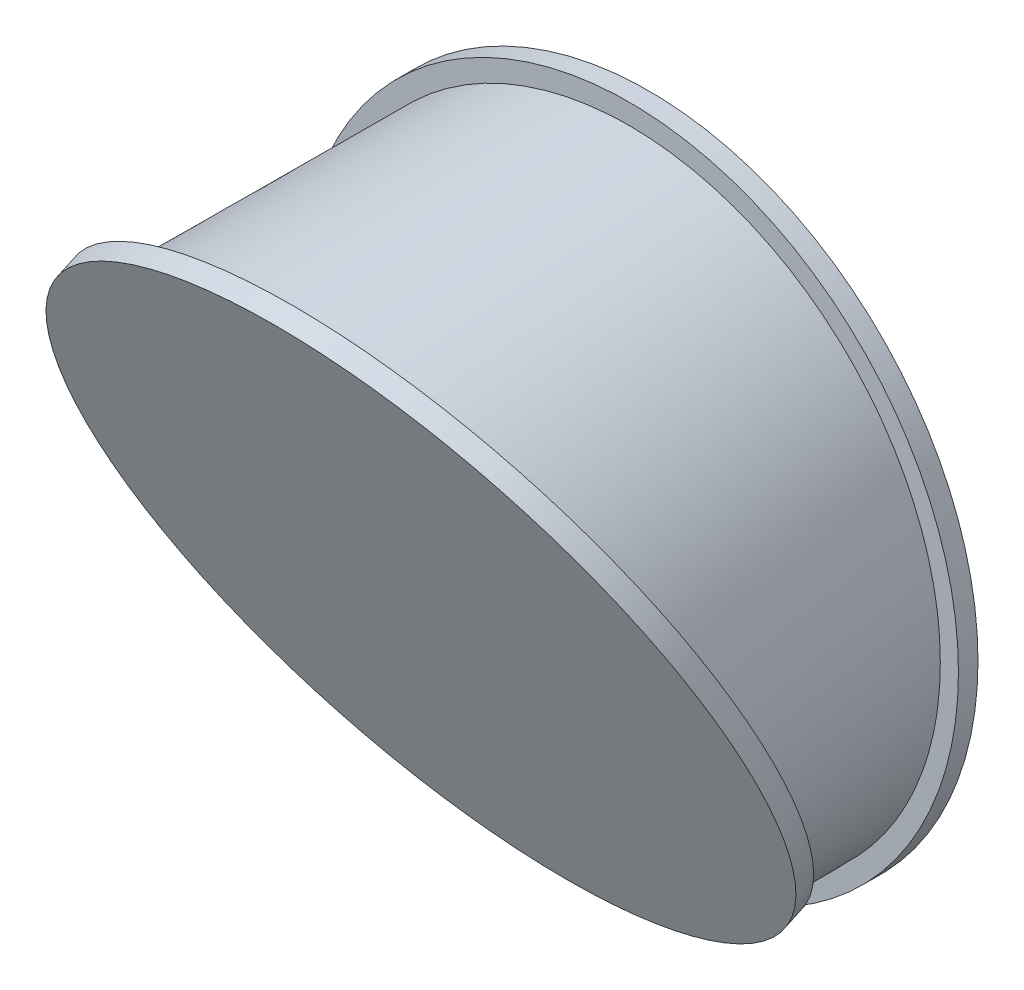
SolidWorks part; units mm, degrees
ref_plane "Front Plane" through (0, 0, 0) normal (0, 0, 1) x (1, 0, 0)
ref_plane "Top Plane" through (0, 0, 0) normal (0, 1, 0) x (1, 0, 0)
ref_plane "Right Plane" through (0, 0, 0) normal (1, 0, 0) x (0, 0, -1)
sketch "Sketch1" plane through (0, 0, 0) normal (0, 0, 1) x (1, 0, 0)
  line L0 (0, 34.9907) -> (0, -37.6588) construction
  line L1 (-13.89, -75) -> (14.3357, -75) construction
  circle A0 centre (0, 0) radius 47.5
  circle A1 centre (0, 0) radius 50.5
  point P8 (0, 47.5)
  dimension "D1" = 95
  dimension "D3" = 3
  dimension "D2" = 75
sketch "Sketch2" plane through (0, 0, 0) normal (1, 0, 0) x (0, 0, -1)
  line L0 (-83.7289, 0) -> (11.8569, 0) construction
ref_plane "Plane1" through (0, -13.3955, 28.7267) normal (0, -0.4226, 0.9063) x (1, 0, 0)
sketch "Sketch3" plane through (0, -13.3955, 28.7267) normal (0, -0.4226, 0.9063) x (1, 0, 0)
  line L0 (0, 14.7803) -> (0, 114.7803)
  line L2 (0, 19.9432) -> (0, -19.0864) construction
  circle A0 centre (0, 14.7803) radius 50
  circle A1 centre (0, 14.7803) radius 53
  point P4 (0, 64.7803)
  dimension "D1" = 100
  dimension "D2" = 3
  dimension "D3" = 100
loft "Loft1" add section "Sketch1" section "Sketch3" connector at (0.2415, 47.4994, 0) connector at (-0.0003, 45.3154, 56.104)
extrude "Boss-Extrude1" add sketch "Sketch3<5>" against normal blind 3 contours A1
sketch "Sketch3<5>" plane through (0, -13.3955, 28.7267) normal (0, -0.4226, 0.9063) x (1, 0, 0) same geometry as "Sketch3"
extrude "Boss-Extrude2" add sketch "Sketch1<4>" along normal blind 3 contours A1
sketch "Sketch1<4>" plane through (0, 0, 0) normal (0, 0, 1) x (1, 0, 0) same geometry as "Sketch1"
